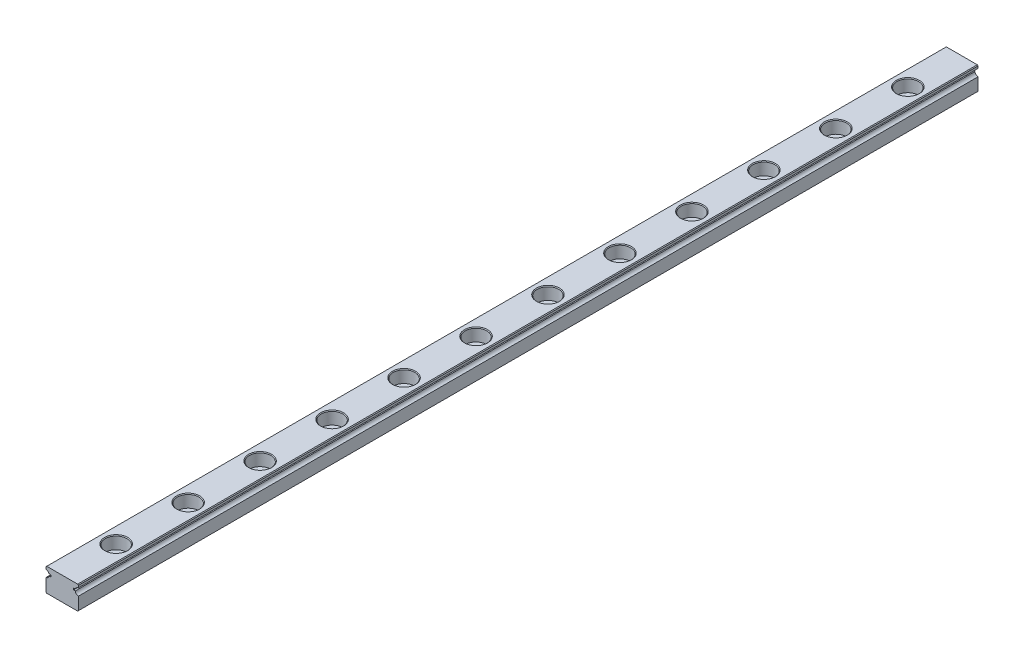
SolidWorks part; units mm, degrees
ref_plane "Спереди" through (0, 0, 0) normal (0, 0, 1) x (1, 0, 0)
ref_plane "Сверху" through (0, 0, 0) normal (0, 1, 0) x (1, 0, 0)
ref_plane "Справа" through (0, 0, 0) normal (1, 0, 0) x (0, 0, -1)
sketch "Sketch1" plane through (0, 0, 0) normal (0, 0, 1) x (1, 0, 0)
  line L0 (0, 0) -> (0, 4.3706) construction
  line L1 (-4.3, -3.25) -> (4.3, -3.25)
  line L2 (-4.5, -3.05) -> (-4.5, 0.455)
  line L3 (-4.3, 3.25) -> (4.3, 3.25)
  line L4 (4.5, -3.05) -> (4.5, 0.455)
  line L5 (-4.5, -3.25) -> (4.5, 3.25) construction
  line L6 (-4.5, 3.25) -> (4.5, -3.25) construction
  line L7 (-4.5, 2.445) -> (-4.5, 3.05)
  line L8 (4.5, 2.445) -> (4.5, 3.05)
  line L9 (-4.5, -3.05) -> (-4.3, -3.25)
  line L10 (4.3, -3.25) -> (4.5, -3.05)
  line L11 (4.3, 3.25) -> (4.5, 3.05)
  line L12 (-4.5, 3.05) -> (-4.3, 3.25)
  line L13 (3.6177, 1.2625) -> (3.1501, 1.2625)
  line L14 (-3.6177, 1.2625) -> (-3.1501, 1.2625)
  line L15 (3.1501, 1.2625) -> (3.1501, 1.7625)
  line L16 (-3.6501, 1.7625) -> (-3.1501, 1.7625)
  line L17 (-3.1501, 1.2625) -> (-3.1501, 1.7625)
  line L18 (3.6501, 1.7625) -> (3.1501, 1.7625)
  arc A0 (-4.5, 2.445) -> (-3.6501, 1.7625) centre (-4.6, 1.45) cw
  arc A1 (4.5, 2.445) -> (3.6501, 1.7625) centre (4.6, 1.45) ccw
  arc A2 (-3.6177, 1.2625) -> (-4.5, 0.455) centre (-4.6, 1.45) cw
  arc A3 (3.6177, 1.2625) -> (4.5, 0.455) centre (4.6, 1.45) ccw
  point P0 (0, 0)
  dimension "D4" = 1
  dimension "D5" = 0.1
  dimension "D1" = 9
  dimension "D2" = 6.5
  dimension "D3" = 1.8
  dimension "D6" = 0.5
  dimension "D7" = 0.5
extrude "Extrude1" add sketch "Sketch1" along normal blind 250
sketch "Sketch2" plane through (0, 3.25, 0) normal (0, 1, 0) x (1, 0, 0)
  line L0 (0, 0) -> (0, -15) construction
  circle A0 centre (0, -15) radius 1.75
  circle A1 centre (0, -15) radius 3
  dimension "D1" = 3.5
  dimension "D2" = 6
  dimension "D3" = 15
extrude "Extrude2" cut sketch "Sketch2" against normal up to next contours A0 region at (0, 3.25, 15)
extrude "Extrude4" cut sketch "Sketch" against normal blind 3.5
sketch "Sketch" plane through (0, 3.25, 0) normal (0, 1, 0) x (1, 0, 0) same geometry as "Sketch2"
chamfer "Chamfer1" distance 0.2 angle 45 2 edges at (0, -3.25, 16.75) (0, 3.25, 18)
pattern_linear "LPattern1" count 12 spacing 20 along (0, 0, 1) of "Extrude4", "Chamfer1", "Extrude2"
